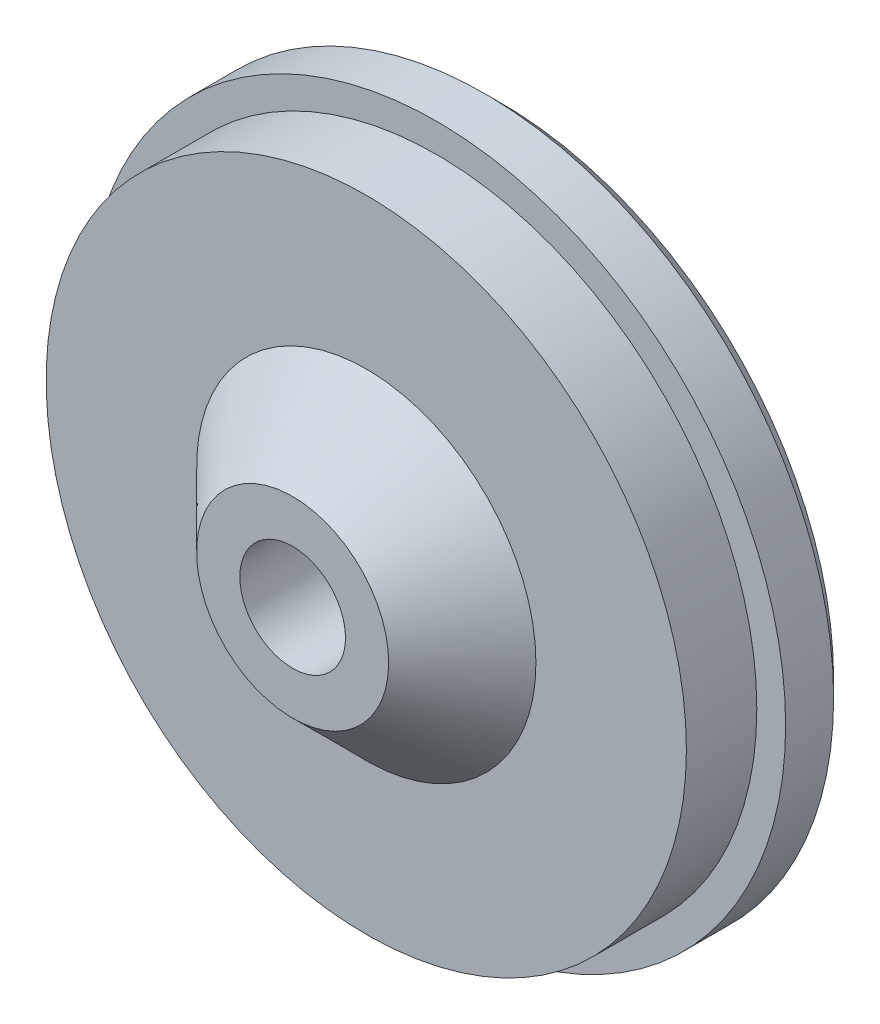
SolidWorks part; units mm, degrees
material "ABS"
ref_plane "Front Plane" through (0, 0, 0) normal (0, 0, 1) x (1, 0, 0)
ref_plane "Top Plane" through (0, 0, 0) normal (0, 1, 0) x (1, 0, 0)
ref_plane "Right Plane" through (0, 0, 0) normal (1, 0, 0) x (0, 0, -1)
sketch "Sketch1" plane through (0, 0, 0) normal (0, 0, 1) x (1, 0, 0)
  circle A0 centre (0, 0) radius 10.9
  dimension "D1" = 21.8
extrude "Boss-Extrude1" add sketch "Sketch1" along normal blind 2
sketch "Sketch2" plane through (0, 0, 2) normal (0, 0, 1) x (1, 0, 0)
  circle A0 centre (0, 0) radius 10
  dimension "D1" = 20
extrude "Boss-Extrude2" add sketch "Sketch2" along normal blind 2.2
sketch "Sketch4" plane through (0, 0, 4.2) normal (0, 0, 1) x (1, 0, 0)
  circle A0 centre (0, 0) radius 3
  dimension "D1" = 6
extrude "Boss-Extrude3" add sketch "Sketch4" along normal blind 2.3
sketch "Sketch3" plane through (0, 0, 0) normal (0, 0, -1) x (-1, 0, 0)
  circle A0 centre (0, 0) radius 1.65
  dimension "D1" = 3.3
extrude "Cut-Extrude1" cut sketch "Sketch3" against normal through all
chamfer "Chamfer1" distance 2.3 angle 45 1 edges at (3, 0, 4.2)
chamfer "Chamfer2" distance 0.5 angle 45 1 edges at (-1.65, 0, 0)
chamfer "Chamfer3" distance 0.5 angle 45 1 edges at (10.9, 0, 0)
